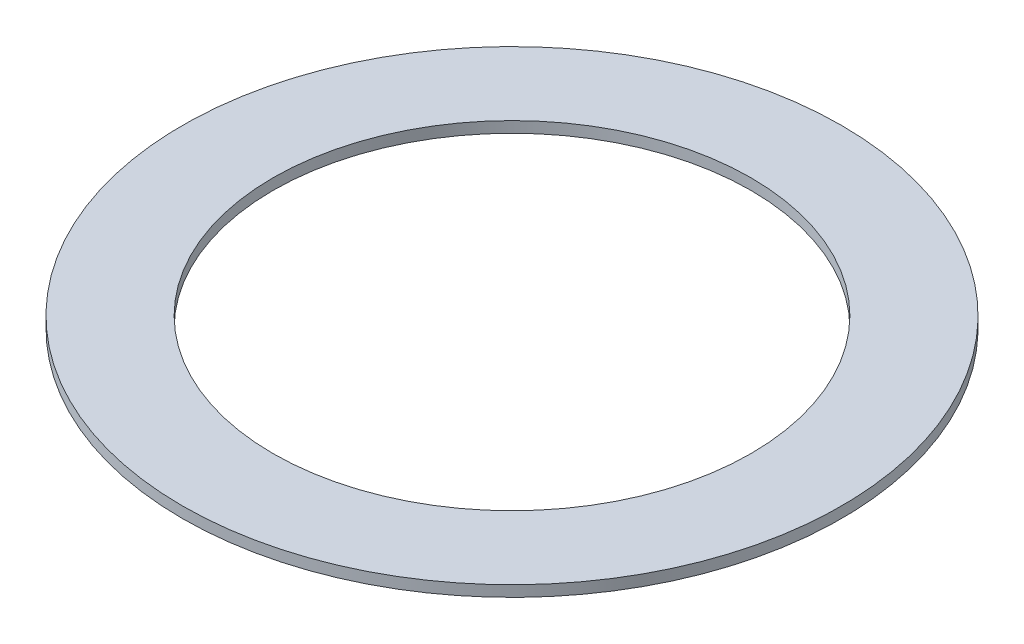
SolidWorks part; units mm, degrees
ref_plane "Front Plane" through (0, 0, 0) normal (0, 0, 1) x (1, 0, 0)
ref_plane "Top Plane" through (0, 0, 0) normal (0, 1, 0) x (1, 0, 0)
ref_plane "Right Plane" through (0, 0, 0) normal (1, 0, 0) x (0, 0, -1)
sketch "Sketch1" plane through (0, 0, 0) normal (0, 1, 0) x (1, 0, 0)
  circle A0 centre (0, 0) radius 60
  circle A1 centre (0, 0) radius 43.5
  dimension "inner diameter" = 87
  dimension "outer diameter" = 120
extrude "Boss-Extrude1" add sketch "Sketch1" along normal mid plane 2
